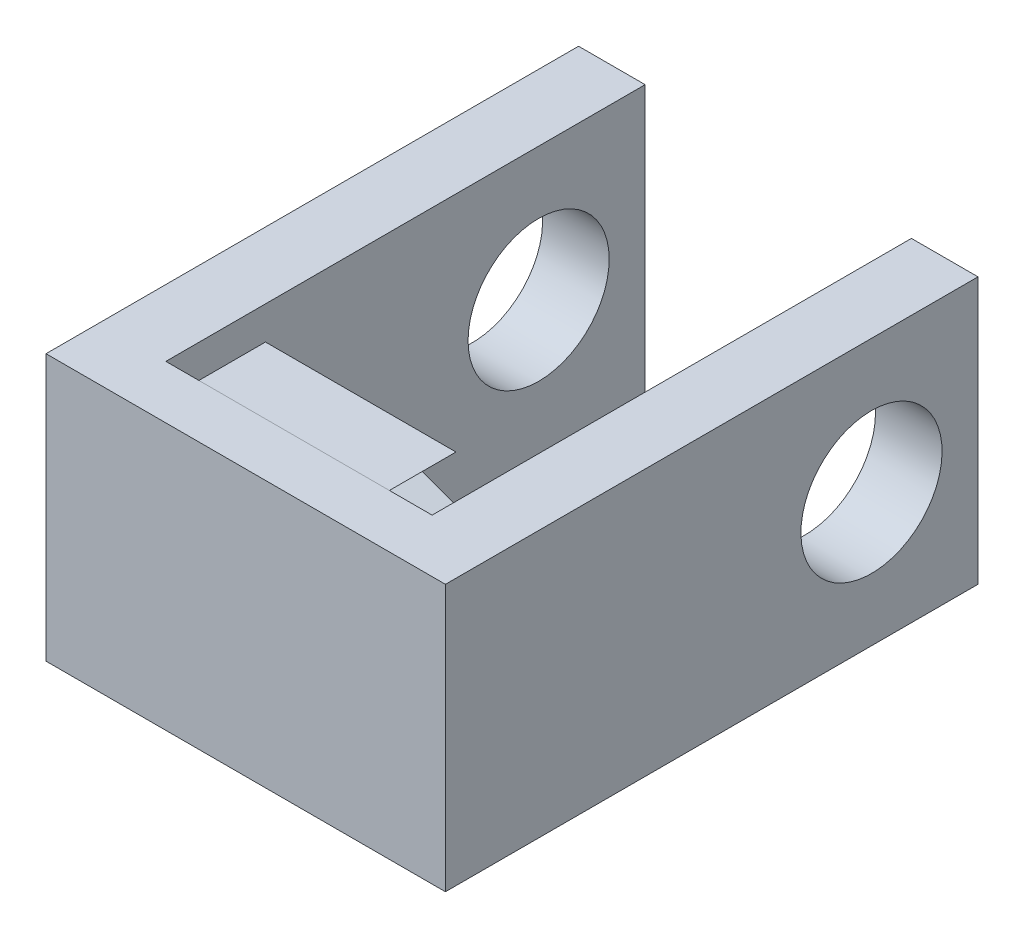
SolidWorks part; units mm, degrees
ref_plane "Front Plane" through (0, 0, 0) normal (0, 0, 1) x (1, 0, 0)
ref_plane "Top Plane" through (0, 0, 0) normal (0, 1, 0) x (1, 0, 0)
ref_plane "Right Plane" through (0, 0, 0) normal (1, 0, 0) x (0, 0, -1)
sketch "Sketch1" plane through (0, 0, 0) normal (0, 0, 1) x (1, 0, 0)
  line L1 (0, 10) -> (15, 10)
  line L2 (0, 10) -> (0, 0)
  line L3 (0, 0) -> (15, 0)
  line L4 (15, 10) -> (15, 0)
  point P4 (7.9839, -4.7782)
  dimension "D1" = 15
  dimension "D2" = 10
extrude "Boss-Extrude1" add sketch "Sketch1" along normal blind 2
sketch "Sketch2" plane through (0, 0, 0) normal (0, 0, -1) x (-1, 0, 0)
  line L0 (-15, 10) -> (0, 10) construction
  line L1 (-15, 0) -> (-12.5, 0)
  line L2 (-15, 0) -> (-15, 10)
  line L3 (-15, 10) -> (-12.5, 10)
  line L4 (-12.5, 0) -> (-12.5, 10)
  line L6 (0, 0) -> (-2.5, 0)
  line L7 (0, 0) -> (0, 10)
  line L8 (0, 10) -> (-2.5, 10)
  line L9 (-2.5, 0) -> (-2.5, 10)
  dimension "D1" = 2.5
  dimension "D2" = 2.5
extrude "Boss-Extrude2" add sketch "Sketch2" along normal blind 18
sketch "Sketch3" plane through (15, 0, 0) normal (1, 0, 0) x (0, 0, -1)
  line L0 (-2, 5) -> (18, 5) construction
  line L1 (-2, 0) -> (-2, 10) construction
  line L2 (18, 10) -> (18, 0) construction
  circle A0 centre (14, 5) radius 2.65
  dimension "D1" = 5.3
  dimension "D2" = 4
extrude "Cut-Extrude1" cut sketch "Sketch3" against normal through all
sketch "Sketch4" plane through (0, 0, 0) normal (0, 0, -1) x (-1, 0, 0)
  line L1 (-3.7416, 0) -> (-3.7416, 10) construction
  line L4 (-9.3918, 1.2748) -> (-11.0416, 0.6743) construction
  line L5 (-11.0416, 0.6743) -> (-11.0416, 0) construction
  line L9 (-10.8958, 10) -> (-9.3918, 9.4526) construction
  line L10 (-9.2816, 9.2953) -> (-9.2816, 8.9719) construction
  line L11 (-9.3918, 8.8146) -> (-11.0416, 8.2141) construction
  line L12 (-11.0416, 8.2141) -> (-11.0416, 7.5398) construction
  line L13 (-11.0416, 7.5398) -> (-9.3918, 6.9393) construction
  line L14 (-9.2816, 6.7821) -> (-9.2816, 6.4586) construction
  line L15 (-9.3918, 6.3013) -> (-11.0416, 5.7008) construction
  line L16 (-11.0416, 5.7008) -> (-11.0416, 5.0265) construction
  line L17 (-11.0416, 5.0265) -> (-9.3918, 4.426) construction
  line L18 (-9.2816, 4.2688) -> (-9.2816, 3.9453) construction
  line L19 (-9.3918, 3.7881) -> (-11.0416, 3.1876) construction
  line L20 (-11.0416, 3.1876) -> (-11.0416, 2.5133) construction
  line L21 (-11.0416, 2.5133) -> (-9.3918, 1.9128) construction
  line L22 (-9.2816, 1.7555) -> (-9.2816, 1.432) construction
  line L24 (-3.7416, 0) -> (-3.7416, 10)
  line L27 (-9.3918, 1.2748) -> (-11.0416, 0.6743)
  line L28 (-11.0416, 0.6743) -> (-11.0416, 0)
  line L32 (-10.8958, 10) -> (-9.3918, 9.4526)
  line L33 (-9.2816, 9.2953) -> (-9.2816, 8.9719)
  line L34 (-9.3918, 8.8146) -> (-11.0416, 8.2141)
  line L35 (-11.0416, 8.2141) -> (-11.0416, 7.5398)
  line L36 (-11.0416, 7.5398) -> (-9.3918, 6.9393)
  line L37 (-9.2816, 6.7821) -> (-9.2816, 6.4586)
  line L38 (-9.3918, 6.3013) -> (-11.0416, 5.7008)
  line L39 (-11.0416, 5.7008) -> (-11.0416, 5.0265)
  line L40 (-11.0416, 5.0265) -> (-9.3918, 4.426)
  line L41 (-9.2816, 4.2688) -> (-9.2816, 3.9453)
  line L42 (-9.3918, 3.7881) -> (-11.0416, 3.1876)
  line L43 (-11.0416, 3.1876) -> (-11.0416, 2.5133)
  line L44 (-11.0416, 2.5133) -> (-9.3918, 1.9128)
  line L45 (-9.2816, 1.7555) -> (-9.2816, 1.432)
  line L46 (-3.7416, 10) -> (-10.8958, 10)
  line L47 (-3.7416, 0) -> (-11.0416, 0)
  arc A0 (-9.2816, 9.2953) -> (-9.3918, 9.4526) centre (-9.449, 9.2953) ccw construction
  arc A1 (-9.3918, 8.8146) -> (-9.2816, 8.9719) centre (-9.449, 8.9719) ccw construction
  arc A2 (-9.2816, 6.7821) -> (-9.3918, 6.9393) centre (-9.449, 6.7821) ccw construction
  arc A3 (-9.3918, 6.3013) -> (-9.2816, 6.4586) centre (-9.449, 6.4586) ccw construction
  arc A4 (-9.2816, 4.2688) -> (-9.3918, 4.426) centre (-9.449, 4.2688) ccw construction
  arc A5 (-9.3918, 3.7881) -> (-9.2816, 3.9453) centre (-9.449, 3.9453) ccw construction
  arc A6 (-9.2816, 1.7555) -> (-9.3918, 1.9128) centre (-9.449, 1.7555) ccw construction
  arc A7 (-9.3918, 1.2748) -> (-9.2816, 1.432) centre (-9.449, 1.432) ccw construction
  arc A8 (-9.2816, 9.2953) -> (-9.3918, 9.4526) centre (-9.449, 9.2953) ccw
  arc A9 (-9.3918, 8.8146) -> (-9.2816, 8.9719) centre (-9.449, 8.9719) ccw
  arc A10 (-9.2816, 6.7821) -> (-9.3918, 6.9393) centre (-9.449, 6.7821) ccw
  arc A11 (-9.3918, 6.3013) -> (-9.2816, 6.4586) centre (-9.449, 6.4586) ccw
  arc A12 (-9.2816, 4.2688) -> (-9.3918, 4.426) centre (-9.449, 4.2688) ccw
  arc A13 (-9.3918, 3.7881) -> (-9.2816, 3.9453) centre (-9.449, 3.9453) ccw
  arc A14 (-9.2816, 1.7555) -> (-9.3918, 1.9128) centre (-9.449, 1.7555) ccw
  arc A15 (-9.3918, 1.2748) -> (-9.2816, 1.432) centre (-9.449, 1.432) ccw
extrude "Boss-Extrude3" add sketch "Sketch4" along normal blind 2.5 separate body
